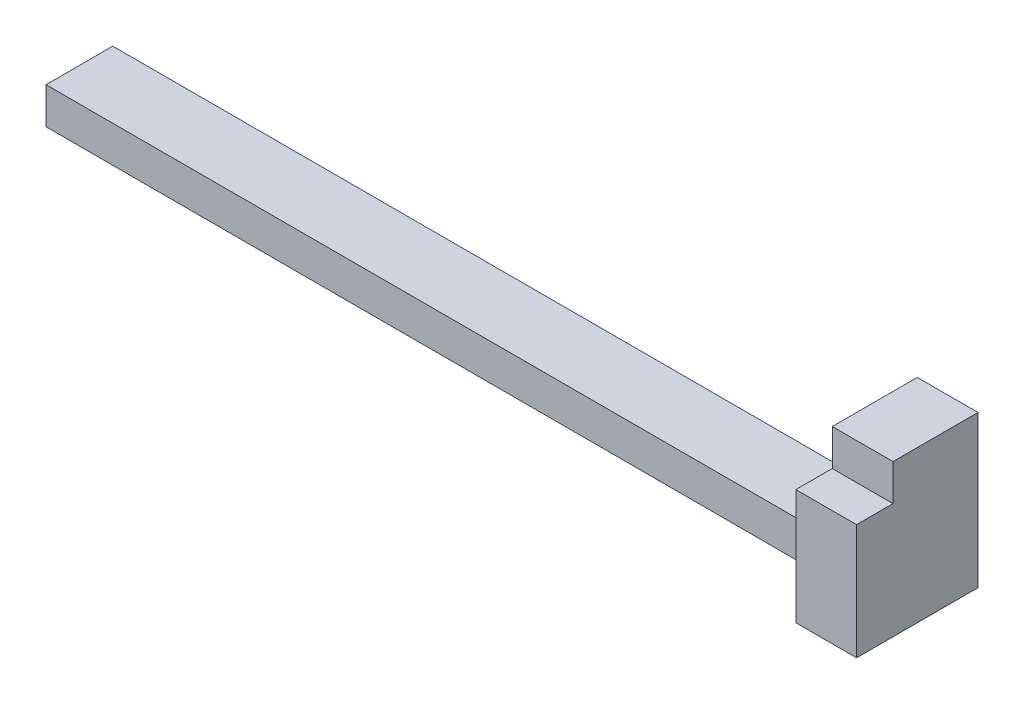
SolidWorks part; units mm, degrees
ref_plane "Front Plane" through (0, 0, 0) normal (0, 0, 1) x (1, 0, 0)
ref_plane "Top Plane" through (0, 0, 0) normal (0, 1, 0) x (1, 0, 0)
ref_plane "Right Plane" through (0, 0, 0) normal (1, 0, 0) x (0, 0, -1)
sketch "Sketch1" plane through (0, 0, 0) normal (1, 0, 0) x (0, 0, -1)
  line L1 (0, 0) -> (11, 0)
  line L2 (0, 0) -> (0, -6)
  line L3 (0, -6) -> (11, -6)
  line L4 (11, 0) -> (11, -6)
  dimension "D1" = 11
  dimension "D2" = 6
extrude "Boss-Extrude1" add sketch "Sketch1" along normal blind 128.5 from offset 73.5 offset against normal yes
sketch "Sketch2" plane through (55, 0, 0) normal (1, 0, 0) x (0, 0, -1)
  line L1 (1, 15) -> (15, 15)
  line L2 (-5, 9) -> (-5, -10)
  line L3 (-5, -10) -> (15, -10)
  line L4 (15, 15) -> (15, -10)
  line L5 (-5, 9) -> (1, 9)
  line L6 (1, 9) -> (1, 15)
  dimension "D2" = 20
  dimension "D3" = 15
  dimension "D4" = 10
extrude "Boss-Extrude2" add sketch "Sketch2" along normal blind 10
sketch "Sketch3" plane through (0, -6, 0) normal (0, -1, 0) x (-1, 0, 0)
  line L0 (-55, 0) -> (73.5, 0) construction
  line L2 (-55, 0) -> (-55, 11) construction
  circle A0 centre (-27.5, 5.5) radius 1.25
  dimension "D1" = 2.5
  dimension "D2" = 5.5
  dimension "D3" = 27.5
extrude "Boss-Extrude3" add sketch "Sketch3" along normal blind 4.5 contours A0
fillet "Fillet1" radius 0.5 1 edges at (27.5, -10.5, -6.75)
